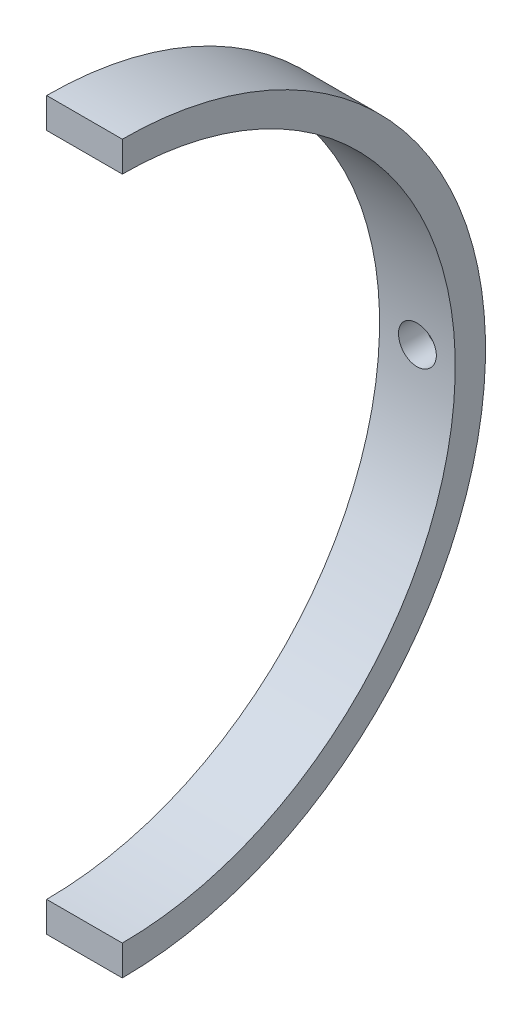
SolidWorks part; units mm, degrees
material "2018 slitina"
ref_plane "Přední rovina" through (0, 0, 0) normal (0, 0, 1) x (1, 0, 0)
ref_plane "Horní rovina" through (0, 0, 0) normal (0, 1, 0) x (1, 0, 0)
ref_plane "Pravá rovina" through (0, 0, 0) normal (1, 0, 0) x (0, 0, -1)
sketch "Skica1" plane through (0, 0, 0) normal (0, 0, 1) x (1, 0, 0)
  line L0 (-358.05, -22) -> (-358.05, 22) construction
  line L1 (-353.05, 24) -> (-353.05, -24) construction
  line L2 (-358.05, -22) -> (-358.05, 22) construction
  line L3 (-353.05, 24) -> (-353.05, -24) construction
  line L4 (-344.9045, 0) -> (-368.3346, 0) construction
  line L5 (-353.05, 24) -> (-358.05, 24)
  line L6 (-353.05, 24) -> (-353.05, 22)
  line L7 (-353.05, 22) -> (-358.05, 22)
  line L8 (-358.05, 24) -> (-358.05, 22)
revolve "Rotovat1" add sketch "Skica1" angle 180 about L4
ref_plane "Rovina1" through (0, 0, -24) normal (0, 0, -1) x (-1, 0, 0)
sketch "Skica2" plane through (0, 0, -24) normal (0, 0, -1) x (-1, 0, 0)
  line L0 (358.05, -24) -> (358.05, 24) construction
  line L1 (353.05, 24) -> (353.05, -24) construction
  line L2 (358.05, -24) -> (358.05, 24) construction
  line L3 (353.05, 24) -> (353.05, -24) construction
  line L4 (353.05, 24) -> (358.05, -24) construction
  point P4 (355.55, 0)
  point P5 (0, 0)
  point P6 (355.05, 0)
hole_wizard "M3 závit1" positions "3DSkica1" profile "Skica3" tap size "M3" standard "ISO" end condition up to next
sketch3d "3DSkica1"
  point P0 (-355.55, 0, -24)
  point P4 (0, 0, 0)
  point P5 (-355.05, 0, -24)
sketch "Skica3" plane through (-355.55, 0, -24) normal (1, 0, 0) x (0, 1, 0)
  line L0 (0, 0) -> (0, 2)
  line L1 (0, 2) -> (1.25, 2)
  line L2 (1.25, 2) -> (1.25, 0.275)
  line L3 (1.25, 0.275) -> (1.525, 0)
  line L5 (1.525, 0) -> (0, 0)
  line L6 (-1.25, 0.275) -> (-1.525, 0) construction
  line L11 (0, -6.35) -> (0, 107.95) construction
  dimension "Průměr závitníku" = 2.5
  dimension "Hloubka závitníku" = 2
  dimension "Průměr blíz. kuž. zahloubení" = 3.05
  dimension "Úhel blíz. kuž. zahloubení" = 90
cosmetic thread "Závit díry1" parameters "D2"=3
